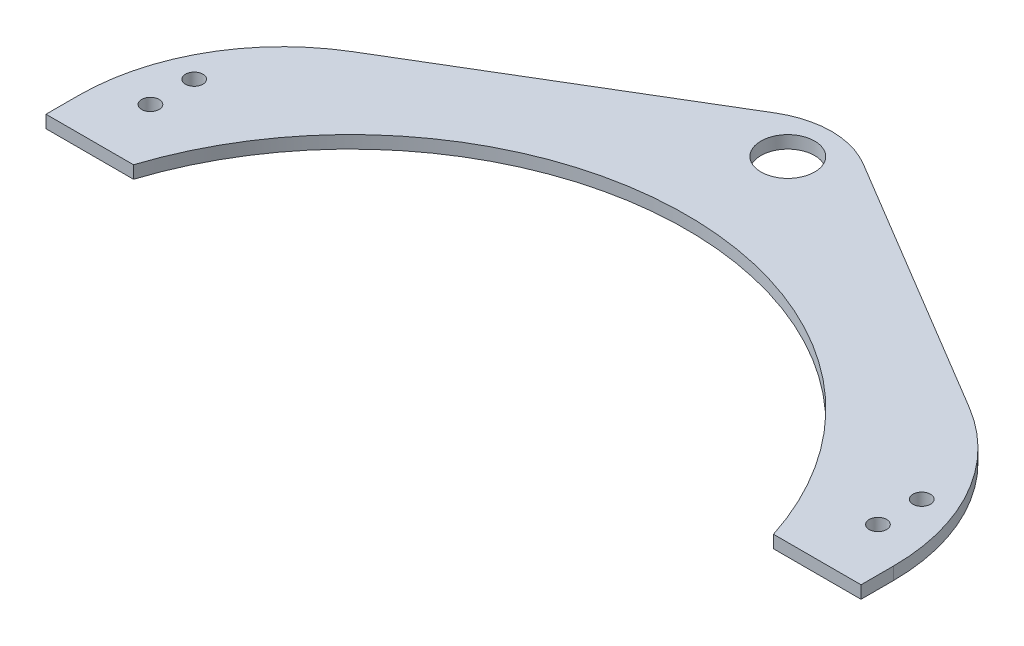
SolidWorks part; units mm, degrees
ref_plane "Front Plane" through (0, 0, 0) normal (0, 0, 1) x (1, 0, 0)
ref_plane "Top Plane" through (0, 0, 0) normal (0, 1, 0) x (1, 0, 0)
ref_plane "Right Plane" through (0, 0, 0) normal (1, 0, 0) x (0, 0, -1)
sketch "Sketch1" plane through (0, 0, 0) normal (0, 1, 0) x (1, 0, 0)
  line L1 (54.85, 0) -> (54.85, 39.9)
  line L2 (109.7, 0) -> (124.7, 0)
  line L3 (0, 0) -> (-15, 0)
  line L4 (124.7, 0) -> (124.7, 16.895)
  line L5 (-15, 0) -> (-15, 16.895)
  line L6 (54.85, 0) -> (54.85, 57.3)
  line L7 (54.85, 57.3) -> (54.85, 64.8)
  line L8 (54.85, 64.8) -> (54.7052, 64.8)
  line L9 (54.85, 64.8) -> (54.9948, 64.8)
  line L10 (62.4068, 62.6719) -> (117.4016, 29.7668)
  line L11 (47.2932, 62.6719) -> (-7.7016, 29.7668)
  line L12 (117.2, 0) -> (117.2, 10.4)
  line L13 (117.2, 10.4) -> (117.2, 17.9)
  line L14 (-7.5, 0) -> (-7.5, 10.4)
  line L15 (107.6704, 35.5893) -> (62.4068, 62.6719)
  line L16 (124.7, 5.5549) -> (124.7, 0)
  line L17 (47.2932, 62.6719) -> (2.0296, 35.5893)
  line L18 (-15, 5.5549) -> (-15, 0)
  line L19 (-7.5, 10.4) -> (-7.5, 17.9)
  circle A1 centre (54.85, 57.3) radius 4.6
  arc A2 (54.7052, 64.8) -> (62.4068, 62.6719) centre (54.7052, 49.8) cw
  arc A3 (54.9948, 64.8) -> (47.2932, 62.6719) centre (54.9948, 49.8) ccw
  arc A4 (-15, 16.895) -> (-7.7016, 29.7668) centre (0, 16.895) cw
  arc A5 (124.7, 16.895) -> (117.4016, 29.7668) centre (109.7, 16.895) ccw
  circle A6 centre (117.2, 17.9) radius 1.5
  circle A7 centre (117.2, 10.4) radius 1.5
  arc A10 (107.6704, 35.5893) -> (124.7, 5.5549) centre (89.7, 5.5549) cw
  arc A11 (2.0296, 35.5893) -> (-15, 5.5549) centre (20, 5.5549) ccw
  circle A13 centre (-7.5, 17.9) radius 1.5
  circle A14 centre (-7.5, 10.4) radius 1.5
  arc A15 (0, 0) -> (109.7, 0) centre (54.85, -17.6788) cw
  point P17 (58.85, 64.8)
  point P20 (50.85, 64.8)
  point P23 (-15, 25.4)
  point P26 (124.7, 25.4)
  point P41 (124.7, 25.4)
  point P44 (-15, 25.4)
  dimension "D8" = 7.5
  dimension "D11" = 15
  dimension "D12" = 15
  dimension "D15" = 10.4
  dimension "D16" = 35
  dimension "D17" = 7.5
  dimension "D1" = 109.7
  dimension "D2" = 39.9
  dimension "D3" = 15
  dimension "D4" = 15
  dimension "D5" = 25.4
  dimension "D6" = 25.4
  dimension "D7" = 57.3
  dimension "D9" = 4
  dimension "D10" = 4
  dimension "D13" = 10.4
  dimension "D14" = 7.5
extrude "Boss-Extrude2" add sketch "Sketch1" along normal blind 3.175 contours L11 A11 L5 L3 A13 L6 A1 L7 L9 A3 | A10 L10 A2 L8 L7 A1 L6 L2 A7 A6 L4 region at (91.5461, 0, -32.6403) region at (18.1539, 0, -32.6403)
sketch "Sketch2" plane through (0, 3.175, 0) normal (0, 1, 0) x (1, 0, 0)
  line L1 (-67.6712, -28.5428) -> (168.2941, -28.5428)
  line L2 (-67.6712, -28.5428) -> (-67.6712, 90.1788)
  line L3 (-67.6712, 90.1788) -> (168.2941, 90.1788)
  line L4 (168.2941, -28.5428) -> (168.2941, 90.1788)
extrude "Cut-Extrude1" cut sketch "Sketch2" against normal blind 1.016
